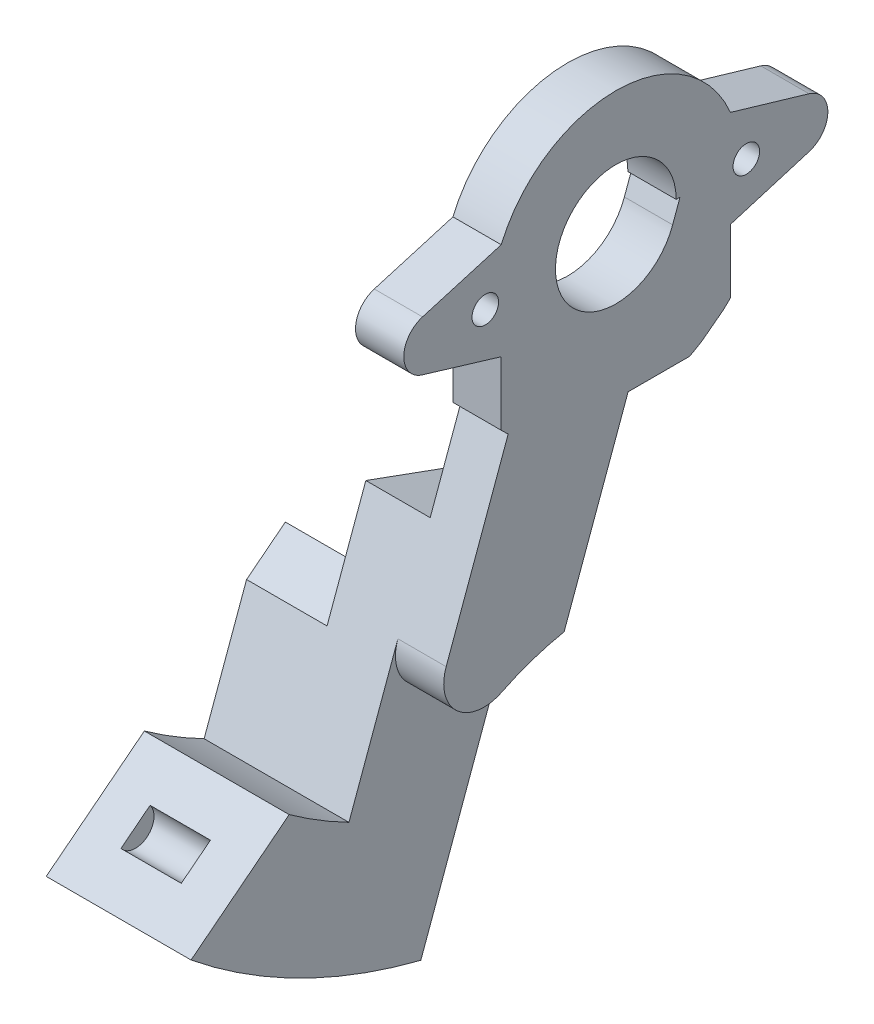
SolidWorks part; units mm, degrees
material "ABS"
ref_plane "Front Plane" through (0, 0, 0) normal (0, 0, 1) x (1, 0, 0)
ref_plane "Top Plane" through (0, 0, 0) normal (0, 1, 0) x (1, 0, 0)
ref_plane "Right Plane" through (0, 0, 0) normal (1, 0, 0) x (0, 0, -1)
sketch "Sketch1" plane through (0, 0, 0) normal (1, 0, 0) x (0, 0, -1)
  line L0 (-52.538, -1.1175) -> (-41.9314, 9.4891)
  line L1 (-7.5, 22.5) -> (7.5, 22.5)
  line L2 (-7.5, 22.5) -> (-7.5, -22.5)
  line L3 (-7.5, -22.5) -> (7.5, -22.5)
  line L4 (7.5, 22.5) -> (7.5, -22.5)
  line L5 (-7.5, 22.5) -> (7.5, -22.5) construction
  line L6 (-7.5, -22.5) -> (7.5, 22.5) construction
  line L7 (-46.7898, -6.2961) -> (-34.5937, 3.2565)
  line L8 (-27.1666, -1.2906) -> (-17.0689, 26.4527)
  line L9 (-17.0689, 26.4527) -> (-2.9735, 21.3224)
  line L10 (-2.9735, 21.3224) -> (-13.0712, -6.4209)
  line L11 (-10.0212, 23.8875) -> (-20.2818, -4.3033) construction
  line L12 (-13.0712, -6.4209) -> (-18.2346, -20.6072)
  arc A2 (-7.5, -22.5) -> (-46.7898, -6.2961) centre (0, 51.4205) cw
  arc A3 (-7.5, -7.4033) -> (-41.9314, 9.4891) centre (0, 51.4205) cw
  arc A4 (-46.7898, -6.2961) -> (-52.538, -1.1175) centre (0, 51.4205) cw
  point P0 (0, 0)
  dimension "D3" = 74.3
  dimension "D4" = 45
  dimension "D7" = 15
  dimension "D9" = 45
  dimension "D1" = 15
  dimension "D2" = 45
  dimension "D5" = 42.5
  dimension "D6" = 51.93
  dimension "D8" = 15
  dimension "D10" = 20
extrude "Boss-Extrude1" add sketch "Sketch1" along normal blind 5
sketch "Sketch2" plane through (5, 0, 0) normal (1, 0, 0) x (0, 0, -1)
  line L0 (-46.7898, -6.2961) -> (-34.5937, 3.2565)
  line L1 (-38.2267, -12.2914) -> (-25.3359, -2.1946)
  line L2 (-2.9735, 21.3224) -> (-18.2346, -20.6072) construction
  line L3 (-17.0689, 26.4527) -> (-2.9735, 21.3224)
  line L4 (-17.0689, 26.4527) -> (-26.2561, 1.2109)
  line L6 (-2.9735, 21.3224) -> (-12.1607, -3.9194)
  line L7 (-46.7898, -6.2961) -> (-34.5937, 3.2565) construction
  line L8 (-46.7898, -6.2961) -> (-34.5937, 3.2565) construction
  line L9 (-27.1666, -1.2906) -> (-17.0689, 26.4527) construction
  arc A0 (-34.5937, 3.2565) -> (-25.3359, -2.1946) centre (0, 51.4205) ccw
  arc A1 (-46.7898, -6.2961) -> (-38.2267, -12.2914) centre (0, 51.4205) ccw
  arc A2 (-34.5937, 3.2565) -> (-27.1666, -1.2906) centre (0, 51.4205) ccw construction
  arc A3 (-46.7898, -6.2961) -> (-18.2346, -20.6072) centre (0, 51.4205) ccw construction
  arc M5 (-46.7898, -6.2961) -> (-18.2346, -20.6072) centre (0, 51.4205) ccw
  arc M10 (-27.1666, -1.2906) -> (-34.5937, 3.2565) centre (0, 51.4205) cw
  line M11 (-34.5937, 3.2565) -> (-46.7898, -6.2961)
  line M21 (-17.0689, 26.4527) -> (-27.1666, -1.2906)
  line M23 (-18.2346, -20.6072) -> (-2.9735, 21.3224)
  line M24 (-2.9735, 21.3224) -> (-17.0689, 26.4527)
  dimension "D1" = 10
extrude "Boss-Extrude2" add sketch "Sketch2" along normal blind 13 contours A0 L1 M10 M11 M5 | A0 L1 M21 M5 M23 M24
sketch "Sketch3" plane through (18, 0, 0) normal (1, 0, 0) x (0, 0, -1)
  line L1 (-34.5937, 3.2565) -> (-46.7898, -6.2961) construction
  circle A0 centre (-40.6917, -1.5198) radius 2.3
  dimension "D1" = 4.6
extrude "Cut-Extrude1" cut sketch "Sketch3" along normal blind 7.5 from offset 13 offset against normal yes
sketch "Sketch4" plane through (18, 0, 0) normal (1, 0, 0) x (0, 0, -1)
  line L0 (-17.0689, 26.4527) -> (-27.1666, -1.2906) construction
  line L1 (-18.2346, -20.6072) -> (-2.9735, 21.3224) construction
  line L3 (-32.33, -15.4769) -> (-7.9815, 51.42)
  line L4 (-7.9815, 51.42) -> (7.9812, 51.42)
  line L5 (-18.2346, -20.6072) -> (7.9812, 51.42)
  line L6 (10.6838, 34.5699) -> (13.3056, 36.5529)
  line L7 (-10.6838, 34.5699) -> (-13.3056, 36.5529)
  line L11 (-2.9735, 21.3224) -> (-17.0689, 26.4527) construction
  line L22 (-14.2413, 57.4149) -> (-24.0176, 54.5378)
  line L23 (-2.2936, 65.2898) -> (-2.2936, 66.7005)
  line L24 (2.2936, 65.2898) -> (-2.2936, 65.2898)
  line L25 (2.2936, 66.7005) -> (2.2936, 65.2898)
  line L26 (24.0176, 54.5378) -> (14.2413, 57.4149)
  line L27 (14.2516, 45.3642) -> (24.0363, 48.3078)
  line L28 (14.2516, 37.4572) -> (14.2516, 45.3642)
  line L29 (12.2999, 37.8825) -> (13.3056, 36.5529)
  line L30 (9.6781, 35.8995) -> (12.2999, 37.8825)
  line L31 (10.6838, 34.5699) -> (9.6781, 35.8995)
  line L32 (-9.165, 33.698) -> (9.165, 33.698)
  line L33 (-9.6781, 35.8995) -> (-10.6838, 34.5699)
  line L34 (-12.2999, 37.8825) -> (-9.6781, 35.8995)
  line L35 (-13.3056, 36.5529) -> (-12.2999, 37.8825)
  line L36 (-14.2516, 45.3642) -> (-14.2516, 37.4572)
  line L37 (-24.0363, 48.3078) -> (-14.2516, 45.3642)
  line L38 (-14.2413, 57.4149) -> (-24.0176, 54.5378)
  line L42 (24.0176, 54.5378) -> (14.2413, 57.4149)
  line L43 (14.2516, 45.3642) -> (24.0363, 48.3078)
  line L44 (14.2516, 37.4572) -> (14.2516, 45.3642)
  line L48 (-9.165, 33.698) -> (9.165, 33.698)
  line L52 (-14.2516, 45.3642) -> (-14.2516, 37.4572)
  line L53 (-24.0363, 48.3078) -> (-14.2516, 45.3642)
  circle A0 centre (0, 51.42) radius 12.7
  circle A1 centre (0, 51.42) radius 7.5
  arc A2 (-2.2936, 66.7005) -> (2.2936, 66.7005) centre (0, 51.42) cw
  circle A3 centre (16.22, 51.42) radius 1.5 construction
  circle A4 centre (-16.22, 51.42) radius 1.5 construction
  circle A5 centre (16.22, 51.42) radius 1.5 construction
  circle A6 centre (-16.22, 51.42) radius 1.5 construction
  circle A7 centre (-16.22, 51.42) radius 1.65
  circle A8 centre (16.22, 51.42) radius 1.65
  arc A9 (-46.7898, -6.2961) -> (-18.2346, -20.6072) centre (0, 51.4205) ccw construction
  arc A10 (-2.2936, 66.7005) -> (-14.2413, 57.4149) centre (0, 51.42) ccw
  arc A11 (14.2413, 57.4149) -> (2.2936, 66.7005) centre (0, 51.42) ccw
  arc A12 (24.0363, 48.3078) -> (24.0176, 54.5378) centre (23.1, 51.42) ccw
  arc A13 (13.3056, 36.5529) -> (14.2516, 37.4572) centre (0, 51.42) ccw
  arc A14 (9.165, 33.698) -> (10.6838, 34.5699) centre (0, 51.42) ccw
  arc A15 (-10.6838, 34.5699) -> (-9.165, 33.698) centre (0, 51.42) ccw
  arc A16 (-14.2516, 37.4572) -> (-13.3056, 36.5529) centre (0, 51.42) ccw
  arc A17 (-24.0176, 54.5378) -> (-24.0363, 48.3078) centre (-23.1, 51.42) ccw
  arc A18 (-2.2936, 66.7005) -> (-14.2413, 57.4149) centre (0, 51.42) ccw
  arc A19 (14.2413, 57.4149) -> (2.2936, 66.7005) centre (0, 51.42) ccw
  arc A20 (24.0363, 48.3078) -> (24.0176, 54.5378) centre (23.1, 51.42) ccw
  arc A21 (13.3056, 36.5529) -> (14.2516, 37.4572) centre (0, 51.42) ccw
  arc A22 (9.165, 33.698) -> (10.6838, 34.5699) centre (0, 51.42) ccw
  arc A23 (-10.6838, 34.5699) -> (-9.165, 33.698) centre (0, 51.42) ccw
  arc A24 (-14.2516, 37.4572) -> (-13.3056, 36.5529) centre (0, 51.42) ccw
  arc A25 (-24.0176, 54.5378) -> (-24.0363, 48.3078) centre (-23.1, 51.42) ccw
  circle A26 centre (-0.4693, -18.5784) radius 31
  arc A27 (-21.0836, 15.4224) -> (-14.1746, 9.2274) centre (-16.3851, 13.7123) ccw
  dimension "D2" = 25.4
  dimension "D3" = 15
  dimension "D5" = 3.3
  dimension "D6" = 62
  dimension "D8" = 5
  dimension "D1" = 29.2995
  dimension "D7" = 70
  dimension "D4" = 0
extrude "Boss-Extrude3" add sketch "Sketch4" along normal blind 6
sketch "Sketch8" plane through (0, 0, 0) normal (-1, 0, 0) x (0, 0, 1)
  line L0 (46.7898, -6.2961) -> (8.8144, 23.4483)
  line L1 (46.7898, -6.2961) -> (34.5937, 3.2565) construction
  line L2 (17.0689, 26.4527) -> (2.9735, 21.3224) construction
  line L3 (17.0689, 26.4527) -> (17.0689, -17.4044)
  line L5 (2.9735, 21.3224) -> (18.2346, -20.6072) construction
  line M3 (2.9735, 21.3224) -> (18.2346, -20.6072)
  line M7 (27.1666, -1.2906) -> (17.0689, 26.4527)
  line M8 (17.0689, 26.4527) -> (2.9735, 21.3224)
extrude "Cut-Extrude2" cut sketch "Sketch8" against normal blind 10 and the other way through all contours L3 L0 M8 M3 | L3 L0 M8 | L3 L0 M7
sketch "Sketch9" plane through (0, 0, 0) normal (-1, 0, 0) x (0, 0, 1)
  line L0 (17.0689, 16.9829) -> (17.0689, -17.4044) construction
  line L1 (46.7898, -6.2961) -> (34.5937, 3.2565) construction
  line L2 (17.0689, -17.4044) -> (18.2346, -20.6072) construction
  circle A0 centre (24.5689, -6.0479) radius 1.65
  circle A1 centre (37.3353, -3.9718) radius 1.65
  arc A2 (18.2346, -20.6072) -> (46.7898, -6.2961) centre (0, 51.4205) ccw construction
  circle A3 centre (21.5769, -15.1711) radius 1.65
  dimension "D1" = 3.3
  dimension "D2" = 62.5
  dimension "D3" = 66.8
  dimension "D4" = 7.5
  dimension "D5" = 4
  dimension "D6" = 70
  dimension "D7" = 5
extrude "Cut-Extrude3" cut sketch "Sketch9" against normal blind 6
